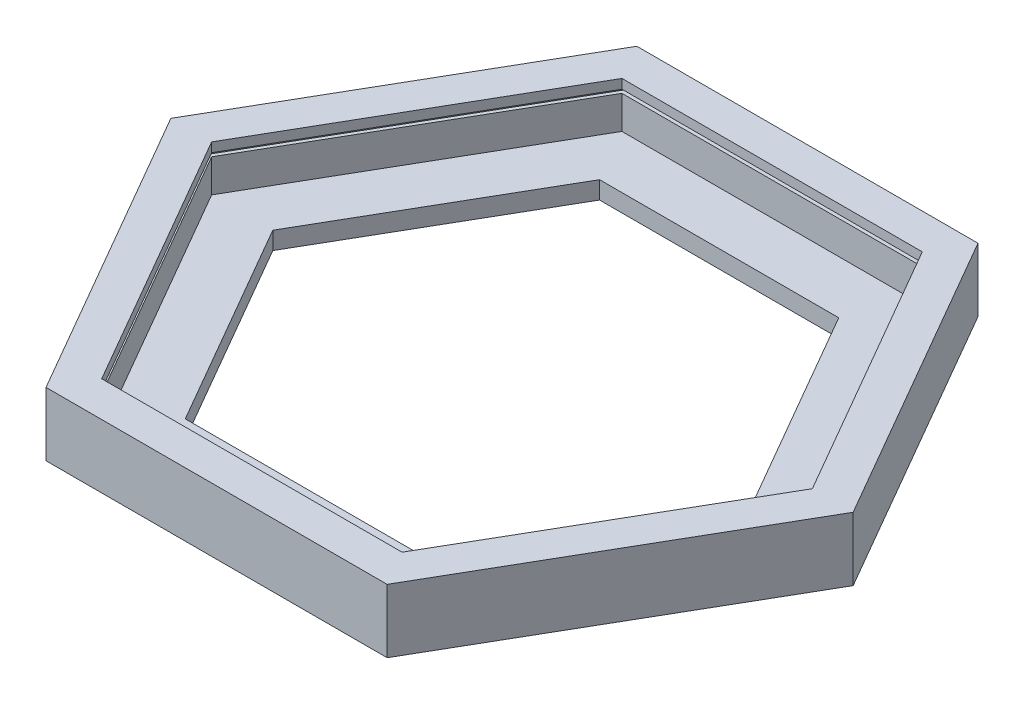
SolidWorks part; units mm, degrees
ref_plane "Front Plane" through (0, 0, 0) normal (0, 0, 1) x (1, 0, 0)
ref_plane "Top Plane" through (0, 0, 0) normal (0, 1, 0) x (1, 0, 0)
ref_plane "Right Plane" through (0, 0, 0) normal (1, 0, 0) x (0, 0, -1)
sketch "Sketch1" plane through (0, 0, 0) normal (0, 1, 0) x (1, 0, 0)
  line L1 (-42.5263, -73.6577) -> (42.5263, -73.6577)
  line L2 (42.5263, -73.6577) -> (85.0526, 0)
  line L3 (85.0526, 0) -> (42.5263, 73.6577)
  line L4 (42.5263, 73.6577) -> (-42.5263, 73.6577)
  line L5 (-42.5263, 73.6577) -> (-85.0526, 0)
  line L6 (-85.0526, 0) -> (-42.5263, -73.6577)
  line L7 (-48.2998, -83.6577) -> (48.2998, -83.6577)
  line L8 (48.2998, -83.6577) -> (96.5996, 0)
  line L9 (96.5996, 0) -> (48.2998, 83.6577)
  line L10 (48.2998, 83.6577) -> (-48.2998, 83.6577)
  line L11 (-48.2998, 83.6577) -> (-96.5996, 0)
  line L12 (-96.5996, 0) -> (-48.2998, -83.6577)
  line L13 (33.866, 58.6577) -> (-33.866, 58.6577)
  line L14 (-33.866, 58.6577) -> (-67.7321, 0)
  line L15 (-67.7321, 0) -> (-33.866, -58.6577)
  line L16 (-33.866, -58.6577) -> (33.866, -58.6577)
  line L17 (33.866, -58.6577) -> (67.7321, 0)
  line L18 (67.7321, 0) -> (33.866, 58.6577)
  circle A0 centre (0, 0) radius 85.0526 construction
  circle A1 centre (0, 0) radius 96.5996 construction
  circle A2 centre (0, 0) radius 58.6577 construction
  dimension "D1" = 85.0526
  dimension "D2" = 10
  dimension "D3" = 15
extrude "Boss-Extrude1" add sketch "Sketch1" along normal blind 5 contours L5 L6 L1 L2 L3 L4 | L11 L12 L7 L8 L9 L10 L6 L5 L4 L3 L2 L1 region at (-61.8406, 0, 35.7037) region at (-70.2363, 0, 40.5509)
extrude "Boss-Extrude2" add sketch "Sketch1<3>" along normal blind 18 contours L11 L12 L7 L8 L9 L10 L6 L5 L4 L3 L2 L1 region at (-70.2363, 0, 40.5509)
sketch "Sketch1<3>" plane through (0, 0, 0) normal (0, 1, 0) x (1, 0, 0) same geometry as "Sketch1"
ref_plane "Plane1" through (0, 14.35, 0) normal (0, 1, 0) x (1, 0, 0)
sketch "Sketch2" plane through (0, 14.35, 0) normal (0, 1, 0) x (1, 0, 0)
  line L1 (85.0526, 0) -> (42.5263, 73.6577)
  line L2 (42.5263, 73.6577) -> (-42.5263, 73.6577)
  line L3 (-42.5263, 73.6577) -> (-85.0526, 0)
  line L4 (-85.0526, 0) -> (-42.5263, -73.6577)
  line L5 (-42.5263, -73.6577) -> (42.5263, -73.6577)
  line L6 (42.5263, -73.6577) -> (85.0526, 0)
  line L7 (86.2073, 0) -> (43.1036, 74.6577)
  line L8 (43.1036, 74.6577) -> (-43.1036, 74.6577)
  line L9 (-43.1036, 74.6577) -> (-86.2073, 0)
  line L10 (-86.2073, 0) -> (-43.1036, -74.6577)
  line L11 (-43.1036, -74.6577) -> (43.1036, -74.6577)
  line L12 (43.1036, -74.6577) -> (86.2073, 0)
  circle A0 centre (0, 0) radius 73.6577 construction
  circle A1 centre (0, 0) radius 74.6577 construction
  dimension "D1" = 1
extrude "Cut-Extrude1" cut sketch "Sketch2" along normal blind 1
